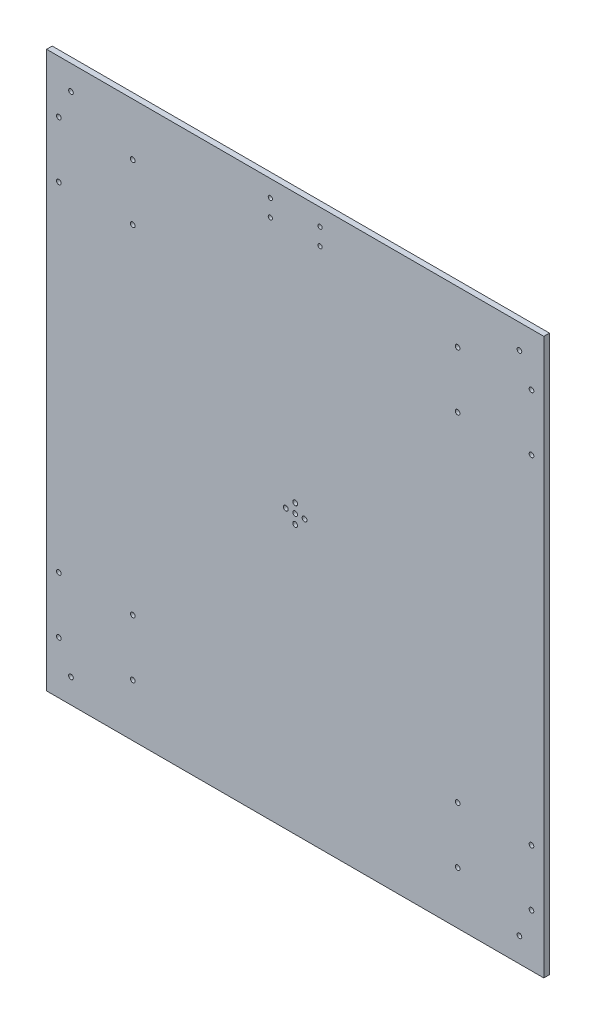
SolidWorks part; units mm, degrees
ref_plane "Спереди" through (0, 0, 0) normal (0, 0, 1) x (1, 0, 0)
ref_plane "Сверху" through (0, 0, 0) normal (0, 1, 0) x (1, 0, 0)
ref_plane "Справа" through (0, 0, 0) normal (1, 0, 0) x (0, 0, -1)
sketch "Эскиз3" plane through (0, 0, 0) normal (0, 0, 1) x (1, 0, 0)
  line L0 (0, 0) -> (0, 10) construction
  line L5 (265, -296.15) -> (-265, -296.15)
  line L6 (265, -296.15) -> (265, 296.15)
  line L7 (265, 296.15) -> (-265, 296.15)
  line L8 (-265, -296.15) -> (-265, 296.15)
  line L9 (0, 0) -> (10, 0) construction
  line L10 (0, 0) -> (0, -10) construction
  line L11 (0, 0) -> (-10, 0) construction
  circle A0 centre (0, 0) radius 2.55
  circle A1 centre (0, 10) radius 2.55
  circle A2 centre (10, 0) radius 2.55
  circle A3 centre (0, -10) radius 2.55
  circle A4 centre (-10, 0) radius 2.55
  point P0 (0, 0)
  point P5 (-265, 0)
  point P6 (0, 296.15)
  point P21 (0, 0)
  dimension "D3" = 5.1
  dimension "D4" = 5.1
  dimension "D1" = 592.3
  dimension "D2" = 530
  dimension "D5" = 10
  dimension "D6" = 4
extrude "Бобышка-Вытянуть1" add sketch "Эскиз3" along normal blind 6
sketch "Эскиз4" plane through (0, 0, 6) normal (0, 0, 1) x (1, 0, 0)
  line L0 (265, 296.15) -> (-265, 296.15) construction
  line L1 (-265, 296.15) -> (-265, -296.15) construction
  circle A0 centre (-239, 270.15) radius 2.5
  dimension "D1" = 5
  dimension "D2" = 26
  dimension "D3" = 26
extrude "Вырез-Вытянуть1" cut sketch "Эскиз4" against normal through all contours A0
pattern_linear "Линейный массив1" count 2 spacing 478 along (1, 0, 0) count 2 spacing 540.3 along (0, -1, 0) of "Вырез-Вытянуть1"
sketch "Эскиз7" plane through (0, 0, 0) normal (0, 0, -1) x (-1, 0, 0)
  line L9 (-26.5, 278.15) -> (26.5, 278.15) construction
  line L10 (-26.5, 278.15) -> (-26.5, 260.15) construction
  line L11 (-26.5, 260.15) -> (26.5, 260.15) construction
  line L16 (26.5, 278.15) -> (26.5, 260.15) construction
  line L17 (-265, 296.15) -> (265, 296.15) construction
  circle A0 centre (-26.5, 278.15) radius 2.25
  circle A1 centre (26.5, 278.15) radius 2.25
  circle A2 centre (-26.5, 260.15) radius 2.25
  circle A3 centre (26.5, 260.15) radius 2.25
  point P4 (0, 260.15)
  dimension "D4" = 4.5
  dimension "D5" = 4.5
  dimension "D6" = 4.5
  dimension "D7" = 4.5
  dimension "D1" = 53
  dimension "D2" = 18
  dimension "D3" = 18
extrude "Вырез-Вытянуть2" cut sketch "Эскиз7" against normal through all
sketch "Эскиз8" plane through (0, 0, 0) normal (0, 0, -1) x (-1, 0, 0)
  line L0 (160, 170.15) -> (265, 250.15) construction
  line L1 (265, 250.15) -> (160, 250.15) construction
  line L2 (265, 250.15) -> (265, 170.15) construction
  line L3 (265, 170.15) -> (160, 170.15) construction
  line L4 (160, 250.15) -> (160, 170.15) construction
  line L5 (160, 250.15) -> (265, 170.15) construction
  line L6 (265, 296.15) -> (265, -296.15) construction
  line L7 (-265, 296.15) -> (265, 296.15) construction
  circle A0 centre (173.125, 180.15) radius 2.5
  circle A1 centre (173.125, 240.15) radius 2.5
  circle A2 centre (251.875, 240.15) radius 2.5
  circle A3 centre (251.875, 180.15) radius 2.5
  dimension "D3" = 5
  dimension "D4" = 5
  dimension "D5" = 5
  dimension "D6" = 5
  dimension "D1" = 105
  dimension "D2" = 80
  dimension "D7" = 60
  dimension "D8" = 46
extrude "Вырез-Вытянуть3" cut sketch "Эскиз8" against normal through all
pattern_linear "Линейный массив2" count 2 spacing 420.3 along (0, -1, 0) count 2 spacing 424.995 along (1, 0, 0) of "Вырез-Вытянуть3"
equation "\"Ширина груза\"= 420"
equation "\"Глубина груза\"= 490"
equation "\"Высота груза\"= 297"
equation "\"Ширина ячейки\"= \"Ширина груза\" + 10"
equation "\"Глубина ячейки\"= \"Глубина груза\" + 10"
equation "\"Высота ячейки\"= \"Высота груза\" + 10 + 13"
equation "\"Колво ячеек ширина\"= 2"
equation "\"Колво ячеек высота\"= 2"
equation "\"Толщина стенки\" = 6"
equation "\"Крепление дверцы\"= 5"
equation "\"Ширина рейки\"= \"Толщина шестерни\""
equation "\"Высота рейки\"= 20"
equation "\"Высота пола\"= 20"
equation "\"Колво полозьев\"= 5"
equation "\"Отступ рейки\"= 20"
equation "\"Глубина каретки\"= \"Глубина ячейки\" + 30 + \"Мотор Y высота корпуса\" + 20"
equation "\"Длинна рейки\"= ( \"Ширина ячейки\" + \"Толщина стенки\" + \"Крепление дверцы\" ) * \"Колво ячеек ширина\" + \"Ширина ячейки выгрузки\" * \"Колво выгрузки\" + \"Толщина стенки\""
equation "\"Отступ шпильки\"= 26"
equation "\"Диаметр шпильки\"= 5"
equation "\"D1@Бобышка-Вытянуть1\" = \"Толщина стенки\""
equation "\"D1@Эскиз4\"= \"Диаметр шпильки\""
equation "\"D2@Эскиз4\"=\"Отступ шпильки\""
equation "\"D3@Эскиз4\"= \"Отступ шпильки\""
equation "\"D2@Эскиз3\"=\"Ширина ячейки\" + \"Ширина пластины\" * 2"
equation "\"D1@Эскиз3\"=\"Глубина каретки\" "
equation "\"D3@Линейный массив1\"=\"Ширина ячейки\"  +\"Ширина пластины\" *2 - \"Отступ шпильки\" * 2"
equation "\"D4@Линейный массив1\"=\"Глубина каретки\" + \"Ширина рейки\" * 2 - \"Отступ шпильки\" * 2 - \"Ширина рейки\" * 2"
equation "\"Длинна шпильки\"= ( \"Высота ячейки\" + \"Толщина стенки\" + \"Высота пола\" ) * \"Колво ячеек высота\" + ( \"Толщина стенки\" + \"Отступ рейки\" ) * 2 "
equation "\"Ширина пластины\"= 50  "
equation "\"Высота зона выгрузки\"= \"Высота ячейки\" * 2 + \"Толщина стенки\" * 2"
equation "\"Колво выгрузки\"= 1"
equation "\"Отступ крепления мотора фиксации\" = 30"
equation "\"Мотор X ширина корпуса\"= 42.3"
equation "\"Мотор X высота корпуса\"= 42.3"
equation "\"Мотор X длина корпуса\"= 40"
equation "\"Мотор X вылет вала\"= 19.8"
equation "\"Мотор Y ширина корпуса\"= 42.3"
equation "\"Мотор Y высота корпуса\"= 42.3"
equation "\"Мотор Y длина корпуса\"= 48"
equation "\"Мотор Y вылет вала\"= 30"
equation "\"Мотор Z ширина корпуса\"= 42"
equation "\"Мотор Z высота корпуса\"= 42"
equation "\"Мотор Z длина корпуса\"= 40"
equation "\"Мотор Z вылет вала\"= 23"
equation "\"Мотор диаметр вала ПРЕДВ\"= 5"
equation "\"Мотор шаг крепления ПРЕДВ\"= 31"
equation "\"Мотор диаметр отверстий ПРЕДВ\"= 3"
equation "\"Мотор глубина отверстий ПРЕДВ\"= 4.5"
equation "\"Мотор диаметр буртика ПРЕДВ\"= 22"
equation "\"Мотор высота буртика ПРЕДВ\"= 2"
equation "\"Мотор диаметр шкива ПРЕДВ\"= 16"
equation "\"Мотор длина шкива ПРЕДВ\"= 12"
equation "\"Мотор отступ шкива ПРЕДВ\"= 5"
equation "\"Мотор X шаг градусов\"= 1.8"
equation "\"Мотор Y шаг градусов\"= 1.8"
equation "\"Мотор Z шаг градусов\"= 1.8"
equation "\"Мотор Y диаметр ротора\"= 25.78"
equation "\"Толщина шестерни\"= 10"
equation "\"Ширина ячейки выгрузки\"= \"Ширина ячейки\" + \"Толщина стенки\" + \"Отступ крепления мотора фиксации\"*2"
